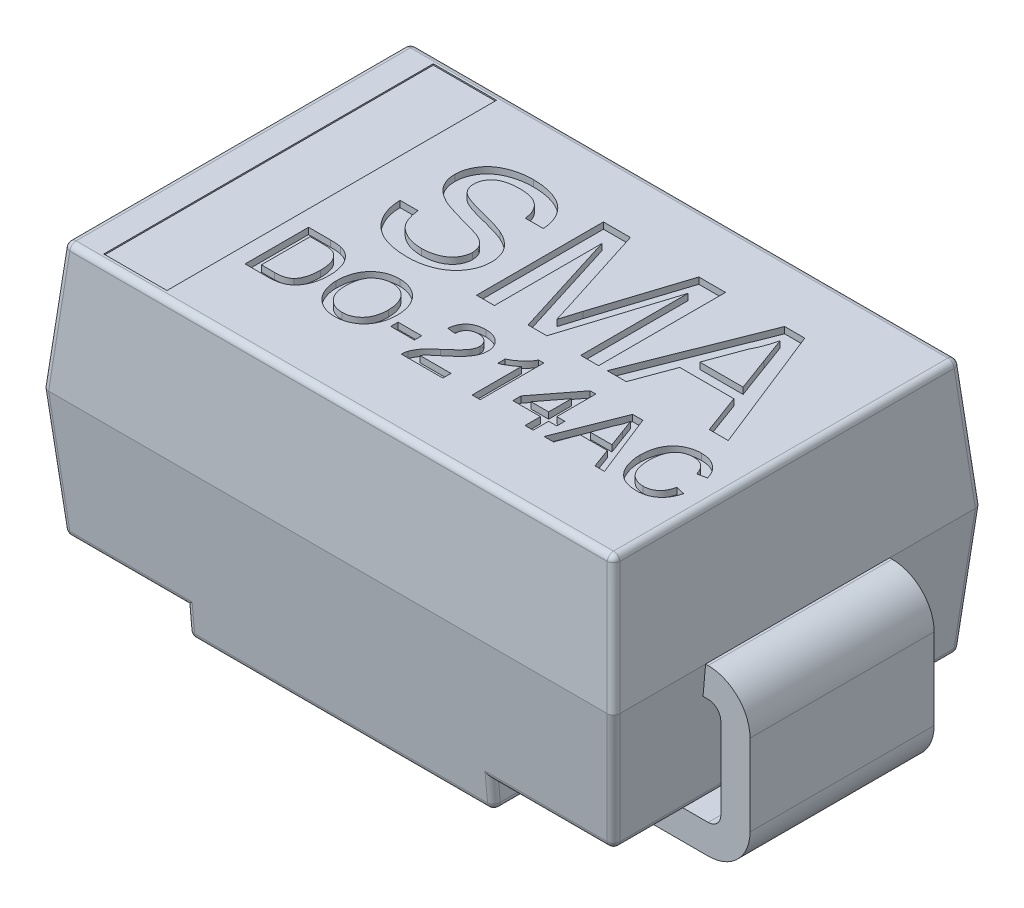
SolidWorks part; units mm, degrees
ref_plane "Спереди" through (0, 0, 0) normal (0, 0, 1) x (1, 0, 0)
ref_plane "Сверху" through (0, 0, 0) normal (0, 1, 0) x (1, 0, 0)
ref_plane "Справа" through (0, 0, 0) normal (1, 0, 0) x (0, 0, -1)
sketch "Sketch1" plane through (0, 0, 0) normal (0, 1, 0) x (1, 0, 0)
  line L1 (-2.25, -1.45) -> (2.25, -1.45)
  line L2 (-2.25, -1.45) -> (-2.25, 1.45)
  line L3 (-2.25, 1.45) -> (2.25, 1.45)
  line L4 (2.25, -1.45) -> (2.25, 1.45)
  line L5 (-2.25, -1.45) -> (2.25, 1.45) construction
  line L6 (-2.25, 1.45) -> (2.25, -1.45) construction
  point P0 (0, 0)
  dimension "D1" = 4.5
  dimension "D2" = 2.9
extrude "Boss-Extrude1" add sketch "Sketch1" along normal blind 1 draft 5 from offset 1.3
extrude "Boss-Extrude2" add sketch "Sketch1<2>" against normal blind 1.23 draft 5 from offset 1.3
sketch "Sketch1<2>" plane through (0, 0, 0) normal (0, 1, 0) x (1, 0, 0) same geometry as "Sketch1"
sketch "Sketch3" plane through (0, 0, 0) normal (0, 0, 1) x (1, 0, 0)
  line L0 (1.2038, 0) -> (-1.2038, 0)
  line L1 (-1.2038, 0) -> (-1.2038, 0.297)
  line L2 (-1.2038, 0.297) -> (-2.27, 0.297)
  line L3 (-2.27, 0.297) -> (-2.27, -0.2052)
  line L4 (-2.27, -0.2052) -> (2.27, -0.2052)
  line L5 (0, 0) -> (0, -0.2052) construction
  line L6 (2.27, 0.297) -> (2.27, -0.2052)
  line L7 (1.2038, 0.297) -> (2.27, 0.297)
  line L8 (1.2038, 0) -> (1.2038, 0.297)
extrude "Cut-Extrude2" cut sketch "Sketch3" against normal mid plane 4
sketch "Sketch2" plane through (0, 0, 0) normal (0, 0, 1) x (1, 0, 0)
  line L0 (2.27, 1.3) -> (-2.27, 1.3)
  line L1 (-2.6, 0.97) -> (-2.6, 0.33)
  line L2 (-2.27, 0) -> (-1.36, 0)
  line L3 (-2.25, 1.3) -> (2.25, 1.3) construction
  line L4 (2.27, 1.07) -> (-2.27, 1.07)
  line L5 (-2.37, 0.97) -> (-2.37, 0.33)
  line L6 (-2.27, 0.23) -> (-1.36, 0.23)
  line L7 (-1.36, 0.23) -> (-1.36, 0)
  line L8 (-2.37, 1.07) -> (-2.37, 0.23) construction
  line L9 (-2.37, 0.23) -> (-1.36, 0.23) construction
  line L10 (0, 1.07) -> (-2.37, 1.07) construction
  line L11 (-2.6, 1.3) -> (-2.6, 0) construction
  line L12 (-2.6, 0) -> (-1.36, 0) construction
  line L13 (0, 1.3) -> (-2.6, 1.3) construction
  line L14 (0, 1.3) -> (0, 0) construction
  line L15 (1.36, 0.23) -> (1.36, 0)
  line L16 (2.27, 0.23) -> (1.36, 0.23)
  line L17 (2.37, 0.97) -> (2.37, 0.33)
  line L18 (2.27, 0) -> (1.36, 0)
  line L19 (2.6, 0.97) -> (2.6, 0.33)
  arc A0 (-2.37, 0.33) -> (-2.27, 0.23) centre (-2.27, 0.33) ccw
  arc A1 (-2.27, 1.07) -> (-2.37, 0.97) centre (-2.27, 0.97) ccw
  arc A2 (-2.6, 0.33) -> (-2.27, 0) centre (-2.27, 0.33) ccw
  arc A3 (-2.27, 1.3) -> (-2.6, 0.97) centre (-2.27, 0.97) ccw
  arc A4 (2.27, 1.3) -> (2.6, 0.97) centre (2.27, 0.97) cw
  arc A5 (2.6, 0.33) -> (2.27, 0) centre (2.27, 0.33) cw
  arc A6 (2.27, 1.07) -> (2.37, 0.97) centre (2.27, 0.97) cw
  arc A7 (2.37, 0.33) -> (2.27, 0.23) centre (2.27, 0.33) cw
  dimension "D2" = 0.1
  dimension "D3" = 0.33
extrude "Boss-Extrude3" add sketch "Sketch2" along normal mid plane 1.45
fillet "Fillet1" radius 0.05 26 edges at (0, 2.3, 1.3625) (-2.1625, 2.3, 0) (0, 2.3, -1.3625) (2.1625, 2.3, 0) (-1.683, 0.297, -1.3623) (-1.2038, 0.1835, -1.3523) (0, 0.07, -1.3424) (1.2038, 0.1835, -1.3523) (1.683, 0.297, -1.3623) (1.2038, 0.07, 0) (-1.2038, 0.07, 0) (1.683, 0.297, 1.3623) (1.2038, 0.1835, 1.3523) (0, 0.07, 1.3424) (-1.2038, 0.1835, 1.3523) (-1.683, 0.297, 1.3623) (-2.1623, 0.297, 0) (2.1623, 0.297, 0) (2.2061, 0.7985, -1.4061) (2.2063, 1.8, -1.4063) (2.2063, 1.8, 1.4063) (2.2061, 0.7985, 1.4061) (-2.2061, 0.7985, 1.4061) (-2.2061, 0.7985, -1.4061) (-2.2063, 1.8, -1.4063) (-2.2063, 1.8, 1.4063)
sketch "Sketch5" plane through (0, 2.3, 0) normal (0, 1, 0) x (1, 0, 0)
  line L0 (-1.669, 0) -> (0, 0) construction
  line L1 (-1.9181, -1.298) -> (-1.42, -1.298)
  line L2 (-1.9181, -1.298) -> (-1.9181, 1.298)
  line L3 (-1.9181, 1.298) -> (-1.42, 1.298)
  line L4 (-1.42, -1.298) -> (-1.42, 1.298)
  line L5 (-1.9181, -1.298) -> (-1.42, 1.298) construction
  line L6 (-1.9181, 1.298) -> (-1.42, -1.298) construction
  point P0 (-1.669, 0)
extrude "Cut-Extrude4" cut sketch "Sketch5" against normal blind 0.01
sketch "Sketch4" plane through (0, 2.3, 0) normal (0, 1, 0) x (1, 0, 0)
  text T0 "SMA" font "Arial" height 1
  text T1 "DO-214AC" font "Arial" height 0.5
extrude "Cut-Extrude3" cut sketch "Sketch4" against normal blind 0.05
